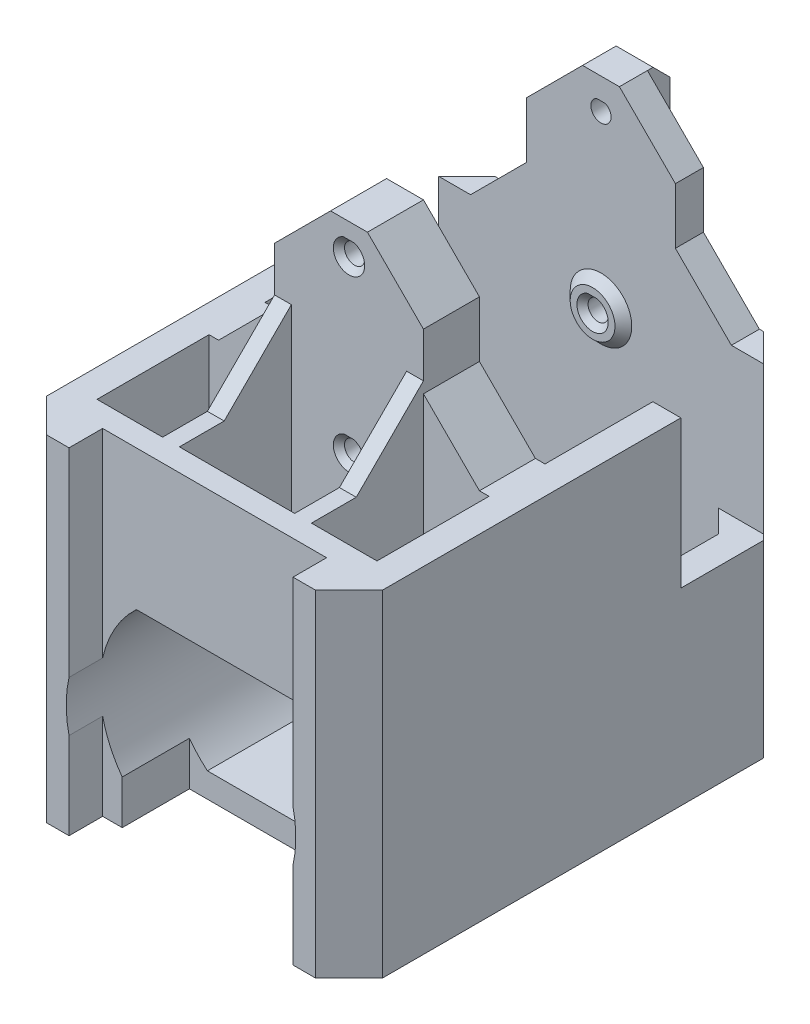
SolidWorks part; units mm, degrees
ref_plane "Front Plane" through (0, 0, 0) normal (0, 0, 1) x (1, 0, 0)
ref_plane "Top Plane" through (0, 0, 0) normal (0, 1, 0) x (1, 0, 0)
ref_plane "Right Plane" through (0, 0, 0) normal (1, 0, 0) x (0, 0, -1)
sketch "Sketch1" plane through (0, 0, 0) normal (0, 0, 1) x (1, 0, 0)
  line L1 (-15, -20) -> (15, -20)
  line L2 (-15, -20) -> (-15, 20)
  line L3 (-15, 20) -> (15, 20)
  line L4 (15, -20) -> (15, 20)
  line L5 (-15, -20) -> (15, 20) construction
  line L6 (-15, 20) -> (15, -20) construction
  point P0 (0, 0)
  dimension "D1" = 30
  dimension "D2" = 40
extrude "Boss-Extrude1" add sketch "Sketch1" along normal blind 40
sketch "Sketch2" plane through (0, 0, 40) normal (0, 0, 1) x (1, 0, 0)
  line L5 (-6.9866, -2.5) -> (6.9866, -2.5)
  line L7 (-6.6464, -17.803) -> (6.6464, -17.803)
  arc A4 (-6.9866, -2.5) -> (-6.6464, -17.803) centre (0, -10) ccw
  arc A5 (6.6464, -17.803) -> (6.9866, -2.5) centre (0, -10) ccw
  point P0 (0, -10)
  dimension "D2" = 20.5
extrude "Cut-Extrude1" cut sketch "Sketch2" against normal blind 35
sketch "Sketch4" plane through (0, 20, 0) normal (0, 1, 0) x (1, 0, 0)
  line L1 (-12.5, -37.5) -> (12.5, -37.5)
  line L2 (-12.5, -37.5) -> (-12.5, -2.5)
  line L3 (-12.5, -2.5) -> (12.5, -2.5)
  line L4 (12.5, -37.5) -> (12.5, -2.5)
  point P0 (0, -20)
  dimension "D1" = 25
  dimension "D2" = 35
extrude "Cut-Extrude3" cut sketch "Sketch4" against normal blind 20
sketch "Sketch5" plane through (0, 0, 0) normal (0, 1, 0) x (1, 0, 0)
  line L0 (12.5, -37.5) -> (12.5, -2.5) construction
  line L1 (-12.5, -2.5) -> (12.5, -2.5)
  line L2 (-12.5, -2.5) -> (-12.5, -20)
  line L3 (-12.5, -20) -> (12.5, -20)
  line L4 (12.5, -2.5) -> (12.5, -20)
extrude "Cut-Extrude4" cut sketch "Sketch5" against normal blind 20
sketch "Sketch13" plane through (0, 0, 0) normal (0, 1, 0) x (1, 0, 0)
  line L0 (12.5, -37.5) -> (12.5, -20) construction
  line L1 (-12.5, -20) -> (12.5, -20)
  line L2 (-12.5, -20) -> (-12.5, -25)
  line L3 (-12.5, -25) -> (12.5, -25)
  line L4 (12.5, -20) -> (12.5, -25)
  dimension "D1" = 5
extrude "Boss-Extrude3" add sketch "Sketch13" along normal up to surface (20 mm away) up to face at (0, 20, 20)
sketch "Sketch8" plane through (0, 0, 40) normal (0, 0, 1) x (1, 0, 0)
  line L0 (-0.5467, -9.1627) -> (0.5467, -9.1627)
  arc A3 (-0.5467, -9.1627) -> (0.5467, -9.1627) centre (0, -10.2278) ccw
extrude "Cut-Extrude5" cut sketch "Sketch8" against normal up to surface (40 mm away) up to face at (0, 0, 0)
sketch "Sketch9" plane through (0, 0, 0) normal (0, 0, -1) x (-1, 0, 0)
  line L6 (-0.3543, 7.8496) -> (0.3543, 7.8496)
  arc A2 (-0.3543, 7.8496) -> (0.3543, 7.8496) centre (0, 7.0222) ccw
extrude "Cut-Extrude6" cut sketch "Sketch9" against normal up to surface (40 mm away) up to face at (0, -10.1897, 40)
sketch "Sketch10" plane through (0, 0, 40) normal (0, 0, 1) x (1, 0, 0)
  line L0 (15, -20) -> (15, 20) construction
  line L1 (-15, 20) -> (15, 20)
  line L2 (-15, 20) -> (-15, 10)
  line L3 (-15, 10) -> (15, 10)
  line L4 (15, 20) -> (15, 10)
  dimension "D1" = 10
extrude "Cut-Extrude9" cut sketch "Sketch10" against normal up to surface (40 mm away) up to face at (0, 6.9859, 0)
chamfer "Chamfer2" distance 3 angle 45 4 edges at (15, -5, 0) (15, -5, 40) (-15, -5, 40) (-15, -5, 0)
sketch "Sketch16" plane through (-12.5, 0, 0) normal (1, 0, 0) x (0, 0, -1)
  line L1 (-2.5, 10) -> (-9.5368, 10)
  line L2 (-2.5, 10) -> (-2.5, -3.1649)
  line L6 (-9.5368, -3.1649) -> (-2.5, -3.1649)
  line L7 (-9.5368, -3.1649) -> (-10.3664, -3.1649)
  line L8 (-10.3664, -3.1649) -> (-10.3664, 10)
  line L9 (-3, 10) -> (-37, 10) construction
  line L10 (-10.3664, 10) -> (-9.5368, 10)
extrude "Cut-Extrude10" cut sketch "Sketch16" against normal mid plane 57
sketch "Sketch17" plane through (0, 10, 0) normal (0, 1, 0) x (1, 0, 0)
  line L0 (12.5, -37.5) -> (12.5, -25) construction
  line L1 (-12.5, -37.5) -> (12.5, -37.5)
  line L2 (-12.5, -37.5) -> (-12.5, -35)
  line L3 (-12.5, -35) -> (12.5, -35)
  line L4 (12.5, -37.5) -> (12.5, -35)
  dimension "D1" = 2.5
extrude "Boss-Extrude4" add sketch "Sketch17" against normal up to surface (10 mm away) up to face at (0, 0, 31.25)
sketch "Sketch18" plane through (0, 10, 0) normal (0, 1, 0) x (1, 0, 0)
  line L0 (-10, -40) -> (10, -40)
  line L1 (-12, -40) -> (12, -40) construction
  line L5 (-10, -40) -> (10, -40)
  line L6 (-10, -40) -> (-10, -37)
  line L7 (-10, -37) -> (10, -37)
  line L8 (10, -40) -> (10, -37)
  point P5 (0, -40)
  line M15 (-12, -40) -> (12, -40)
  dimension "D1" = 20
  dimension "D2" = 3
extrude "Cut-Extrude13" cut sketch "Sketch18" against normal up to surface (30 mm away) contours L8 L7 L6 M15 region at (0, 10, 38.5) up to face at (0, -20, 11.25)
sketch "Sketch19" plane through (0, -20, 0) normal (0, -1, 0) x (1, 0, 0)
  line L0 (-8.25, 37) -> (8.25, 37)
  line L1 (10, 37) -> (-10, 37) construction
  line L5 (-8.25, 37) -> (8.25, 37)
  line L6 (-8.25, 37) -> (-8.25, 31)
  line L7 (-8.25, 31) -> (8.25, 31)
  line L8 (8.25, 37) -> (8.25, 31)
  point P5 (0, 37)
  line M18 (10, 37) -> (-10, 37)
  dimension "D1" = 16.5
  dimension "D2" = 6
extrude "Cut-Extrude14" cut sketch "Sketch19" against normal blind 10 contours L8 L6 L7 M18 region at (0, -20, 34)
sketch "Sketch20" plane through (0, 0, 20) normal (0, 0, -1) x (-1, 0, 0)
  line L0 (10.25, -10) -> (12.5, -10)
  line L1 (-12.5, -10) -> (-10.25, -10)
  line L2 (-12.5, -10) -> (-12.5, -20)
  line L3 (-12.5, -20) -> (12.5, -20)
  line L4 (12.5, -20) -> (12.5, 10)
  line L5 (12.5, 10) -> (-12.5, 10)
  line L6 (-12.5, 10) -> (-12.5, -20)
  line L7 (-12.5, -20) -> (12.5, -20)
  line L8 (12.5, -20) -> (12.5, -10)
  line L10 (-12.5, -10) -> (-12.5, -20)
  line L11 (-12.5, -20) -> (12.5, -20)
  line L12 (12.5, -10) -> (12.5, -20)
  line L13 (-6.6464, -17.803) -> (6.6464, -17.803)
  arc A0 (6.6464, -17.803) -> (6.9866, -2.5) centre (0, -10) ccw construction
  arc A1 (6.6464, -17.803) -> (10.25, -10) centre (0, -10) ccw
  arc A2 (-6.9866, -2.5) -> (-6.6464, -17.803) centre (0, -10) ccw construction
  arc A3 (-10.25, -10) -> (-6.6464, -17.803) centre (0, -10) ccw
  line M7 (12.5, -20) -> (12.5, 10)
  line M9 (-12.5, 10) -> (-12.5, -20)
  line M10 (-12.5, -20) -> (12.5, -20)
  line M11 (6.6464, -17.803) -> (-6.6464, -17.803)
  arc M12 (-6.6464, -17.803) -> (-6.9866, -2.5) centre (0, -10) cw
  arc M14 (6.9866, -2.5) -> (6.6464, -17.803) centre (0, -10) cw
  dimension "D1" = 0
extrude "Boss-Extrude5" add sketch "Sketch20" along normal blind 8.5 contours L1 L0 M9 M10 M7 M14 M11 M12 region at (-11.375, -10.2693, 20)
sketch "Sketch22" plane through (0, 0, 11.5) normal (0, 0, -1) x (-1, 0, 0)
  line L0 (12.5, -20) -> (12.5, -10) construction
  line L1 (-12.5, -20) -> (12.5, -20)
  line L2 (-12.5, -20) -> (-12.5, -15)
  line L3 (-12.5, -15) -> (12.5, -15)
  line L4 (12.5, -20) -> (12.5, -15)
extrude "Boss-Extrude6" add sketch "Sketch22" along normal blind 1
sketch "Sketch23" plane through (0, 10, 0) normal (0, 1, 0) x (1, 0, 0)
  line L0 (-12.5, -10.5) -> (12.5, -10.5) construction
  line L3 (-6.6464, -25) -> (6.6464, -25)
  line L4 (6.6464, 0) -> (6.6464, -2.5)
  line L5 (-6.6464, 0) -> (-6.6464, -2.5)
  line L6 (-6.6464, -2.5) -> (0, -2.5)
  line L7 (-12.5, -25) -> (12.5, -25) construction
  line L8 (12.5, -25) -> (-12.5, -25) construction
  line L9 (-6.6464, -20) -> (6.6464, -20)
  line L10 (-12.5, -20) -> (12.5, -20) construction
  line L11 (-6.6464, 0) -> (6.6464, 0)
  line L12 (-12, 0) -> (12, 0) construction
  line L14 (14.5, -2.5) -> (-14.5, -2.5) construction
  line L15 (0, -2.5) -> (6.6464, -2.5)
  line L17 (-6.6464, -20) -> (-6.6464, -25)
  line L18 (6.6464, -20) -> (6.6464, -25)
  point P0 (0, -10.5)
  point P16 (0, -20)
  point P21 (0, 0)
extrude "Boss-Extrude7" add sketch "Sketch23" along normal blind 15
chamfer "Chamfer4" distance 5 angle 45 4 edges at (-6.6464, 10, 22.5) (-6.6464, 10, 1.25) (6.6464, 10, 22.5) (6.6464, 10, 1.25)
chamfer "Chamfer6" distance 5 angle 45 4 edges at (-6.6464, 25, 1.25) (-6.6464, 25, 22.5) (6.6464, 25, 1.25) (6.6464, 25, 22.5)
sketch "Sketch30" plane through (0, 0, 0) normal (0, 1, 0) x (1, 0, 0)
  line L0 (12.5, -35) -> (-12.5, -35) construction
  line L1 (-6.6464, -25) -> (-5.1464, -25)
  line L2 (-6.6464, -25) -> (-6.6464, -35)
  line L8 (-6.6464, -35) -> (-5.1464, -35)
  line L9 (-5.1464, -25) -> (-5.1464, -35)
  line L10 (12.5, -35) -> (-12.5, -35) construction
  line L11 (6.6464, -25) -> (5.1464, -25)
  line L12 (6.6464, -25) -> (6.6464, -35)
  line L13 (6.6464, -35) -> (5.1464, -35)
  line L14 (5.1464, -25) -> (5.1464, -35)
  point P6 (0, -28.5004)
  dimension "D2" = 1.5
  dimension "D3" = 1.5
extrude "Boss-Extrude8" add sketch "Sketch30" along normal blind 20
chamfer "Chamfer10" distance 14 2 edges at (5.8964, 20, 35) (-5.8964, 20, 35)
sketch "Sketch29" plane through (0, 0, 0) normal (0, 0, -1) x (-1, 0, 0)
  line L2 (-0.4034, 23.0745) -> (0.4034, 23.0745)
  arc A1 (-0.4034, 23.0745) -> (0.4034, 23.0745) centre (0, 22.27) ccw
extrude "Cut-Extrude15" cut sketch "Sketch29" against normal blind 25
chamfer "Chamfer11" distance 2 angle 45 2 edges at (12.5, -11.5824, 2.5) (-12.5, -11.5824, 2.5)
sketch "Sketch31" plane through (0, 0, 2.5) normal (0, 0, 1) x (1, 0, 0)
  line L0 (-0.3543, 7.8496) -> (0.3543, 7.8496) construction
  line L1 (-0.3543, 7.8496) -> (0.3543, 7.8496)
  circle A0 centre (0, 7.0222) radius 2
  arc A1 (-0.3543, 7.8496) -> (0.3543, 7.8496) centre (0, 7.0222) ccw construction
  arc A2 (-0.3543, 7.8496) -> (0.3543, 7.8496) centre (0, 7.0222) ccw
extrude "Boss-Extrude9" add sketch "Sketch31" along normal blind 0.75
chamfer "Chamfer12" distance 0.5 angle 45 1 edges at (0, 6.1222, 3.25)
chamfer "Chamfer13" distance 0.5 angle 45 1 edges at (0, 7.8496, 3.25)
chamfer "Chamfer14" distance 0.75 angle 45 1 edges at (-2, 7.0222, 2.5)
chamfer "Chamfer15" distance 0.5 angle 45 4 edges at (0, 6.1222, 25) (0, 21.37, 25) (0, 7.8496, 25) (0, 23.0745, 25)
sketch "Sketch32" plane through (0, 0, 0) normal (0, 0, -1) x (-1, 0, 0)
  line L0 (0.4034, 23.0745) -> (-0.4034, 23.0745) construction
  line L1 (-1.6464, 19.54) -> (1.6464, 19.54)
  line L2 (-1.6464, 19.54) -> (-1.6464, 25)
  line L3 (-1.6464, 25) -> (1.6464, 25)
  line L4 (1.6464, 19.54) -> (1.6464, 25)
  line L5 (-1.6464, 19.54) -> (1.6464, 25) construction
  line L6 (-1.6464, 25) -> (1.6464, 19.54) construction
  line L7 (0.4034, 23.0745) -> (-0.4034, 23.0745)
  arc A0 (-0.4034, 23.0745) -> (0.4034, 23.0745) centre (0, 22.27) ccw construction
  arc A1 (-0.4034, 23.0745) -> (0.4034, 23.0745) centre (0, 22.27) ccw
  point P0 (0, 22.27)
extrude "Boss-Extrude10" add sketch "Sketch32" along normal blind 2
chamfer "Chamfer16" distance 3 angle 45 1 edges at (0, 19.54, 0)
chamfer "Chamfer17" distance 1.5 angle 45 1 edges at (0, 25, -2)
